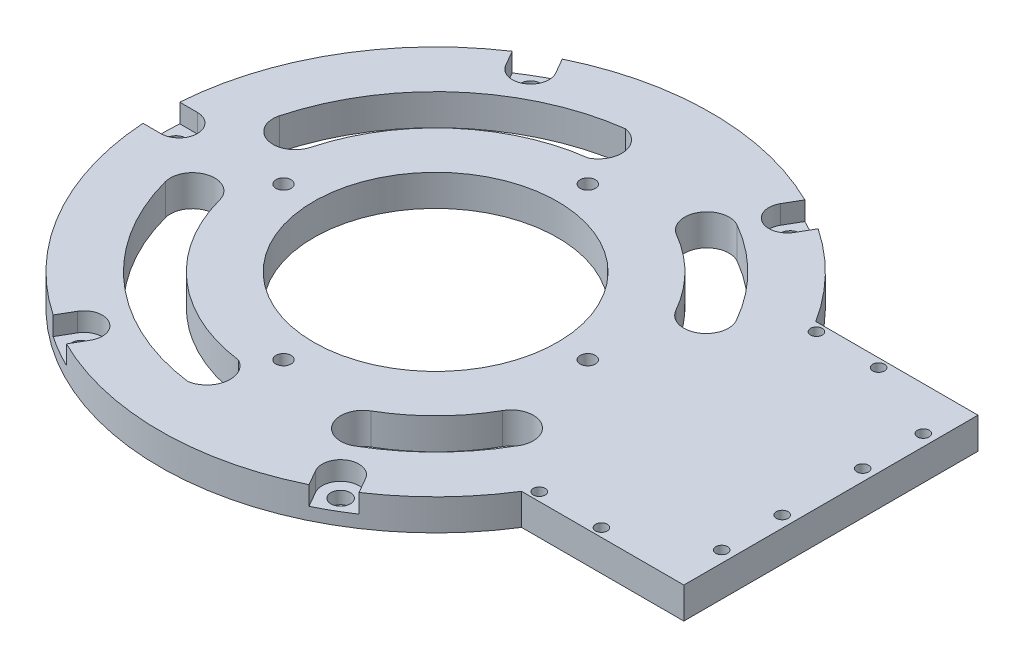
SolidWorks part; units mm, degrees
note: '?' marks a value the reader was unsure of.
material "6061 Alloy"
ref_plane "Front Plane" through (0, 0, 0) normal (0, 0, 1) x (1, 0, 0)
ref_plane "Top Plane" through (0, 0, 0) normal (0, 1, 0) x (1, 0, 0)
ref_plane "Right Plane" through (0, 0, 0) normal (1, 0, 0) x (0, 0, -1)
sketch "Sketch1" plane through (0, 0, 0) normal (0, 1, 0) x (1, 0, 0)
  line L0 (164.381, 61.17) -> (96.9054, 61.17)
  line L1 (96.9054, -61.17) -> (164.381, -61.17)
  line L2 (164.381, -61.17) -> (164.381, 61.17)
  arc A0 (96.9054, 61.17) -> (96.9054, -61.17) centre (0, 0) ccw
extrude "Boss-Extrude1" add sketch "Sketch1" against normal blind 13
sketch "Sketch2" plane through (0, -13, 0) normal (0, -1, 0) x (1, 0, 0)
  arc A0 (36.6644, -63.4908) -> (45.9149, -79.5096) centre (41.2896, -71.5002) ccw
  arc A1 (45.9149, -79.5096) -> (79.9701, -45.108) centre (0, 0) ccw
  arc A2 (79.9701, -45.108) -> (63.8586, -36.0201) centre (71.9144, -40.564) ccw
  arc A3 (63.8586, -36.0201) -> (36.6644, -63.4908) centre (0, 0) cw
extrude "Cut-Extrude1" cut sketch "Sketch2" against normal through all
sketch "Sketch3" plane through (0, -13, 0) normal (0, -1, 0) x (1, 0, 0)
  arc A0 (45.9149, 79.5096) -> (36.6644, 63.4908) centre (41.2896, 71.5002) ccw
  arc A1 (36.6644, 63.4908) -> (63.8586, 36.0201) centre (0, 0) cw
  arc A2 (63.8586, 36.0201) -> (79.9701, 45.108) centre (71.9144, 40.564) ccw
  arc A3 (79.9701, 45.108) -> (45.9149, 79.5096) centre (0, 0) ccw
extrude "Cut-Extrude2" cut sketch "Sketch3" against normal through all
sketch "Sketch4" plane through (0, -13, 0) normal (0, -1, 0) x (1, 0, 0)
  arc A0 (-12.0097, -91.0259) -> (-9.2761, -72.7277) centre (-13.7612, -81.411) ccw
  arc A1 (-9.2761, -72.7277) -> (-70.8237, -18.957) centre (0, 0) cw
  arc A2 (-70.8237, -18.957) -> (-88.6926, -23.7399) centre (-79.7581, -21.3484) ccw
  arc A3 (-88.6926, -23.7399) -> (-12.0097, -91.0259) centre (0, 0) ccw
extrude "Cut-Extrude3" cut sketch "Sketch4" against normal through all
sketch "Sketch5" plane through (0, -13, 0) normal (0, -1, 0) x (1, 0, 0)
  arc A0 (-88.6926, 23.7399) -> (-70.8237, 18.957) centre (-79.7581, 21.3484) ccw
  arc A1 (-70.8237, 18.957) -> (-9.2761, 72.7277) centre (0, 0) cw
  arc A2 (-9.2761, 72.7277) -> (-12.0097, 91.0259) centre (-13.7612, 81.411) ccw
  arc A3 (-12.0097, 91.0259) -> (-88.6926, 23.7399) centre (0, 0) ccw
extrude "Cut-Extrude4" cut sketch "Sketch5" against normal through all
sketch "Sketch6" plane through (0, 0, 0) normal (0, 1, 0) x (-1, 0, 0)
  line L0 (114.3626, 7.3237) -> (106.9962, 7.3428)
  line L1 (106.9567, -7.8972) -> (114.3231, -7.9163)
  arc A0 (106.9962, 7.3428) -> (106.9567, -7.8972) centre (106.9765, -0.2772) ccw
  arc A1 (114.3231, -7.9163) -> (114.3626, 7.3237) centre (0, 0) ccw
extrude "Cut-Extrude5" cut sketch "Sketch6" against normal blind 7.8
hole_wizard "1/4 Clearance Hole1" positions "Sketch10" profile "Sketch9" hole size "1/4" standard "ANSI Inch"
sketch "Sketch10" plane through (0, -7.8, 0) normal (0, 1, 0) x (1, 0, 0)
  circle A0 centre (0, 0) radius 107.95
  point P10 (-107.95, 0)
  point P18 (-53.975, 93.4874)
  point P19 (53.975, 93.4874)
  point P25 (53.975, -93.4874)
  point P26 (-53.975, -93.4874)
  point P28 (107.95, 0) [skipped]
  dimension "D1" = 215.9
  dimension "D2" = 6
sketch "Sketch9" plane through (-53.975, -7.8, 93.4874) normal (1, 0, 0) x (0, 0, 1)
  line L0 (0, 0) -> (0, 5.2)
  line L1 (0, 5.2) -> (4.064, 5.2)
  line L2 (4.064, 5.2) -> (4.064, 0)
  line L5 (4.064, 0) -> (0, 0)
  line L11 (0, -6.35) -> (0, 107.95) construction
  dimension "Thru Hole Dia." = 8.128
  dimension "Thru Hole Depth" = 5.2
hole_wizard "Hole1" positions "Sketch12" profile "Sketch11" legacy
sketch "Sketch12" plane through (0, 0, 0) normal (0, 1, 0) x (1, 0, 0)
  point P0 (63.27, 0)
  point P1 (0, -63.27)
  point P2 (-63.27, 0)
  point P3 (0, 63.27)
sketch "Sketch11" plane through (63.27, 0, 0) normal (1, 0, 0) x (0, 0, 1)
  line L0 (0, 0) -> (0, 13)
  line L1 (0, 13) -> (3.15, 13)
  line L2 (3.15, 13) -> (3.15, 0)
  line L3 (3.15, 0) -> (0, 0)
  line L4 (0, 110) -> (0, -10) construction
  dimension "Diameter" = 6.3
  dimension "Depth" = 13
hole_wizard "Hole2" positions "Sketch14" profile "Sketch13" legacy
sketch "Sketch14" plane through (0, 0, 0) normal (0, 1, 0) x (1, 0, 0)
  point P0 (0, 0)
sketch "Sketch13" plane through (0, 0, 0) normal (1, 0, 0) x (0, 0, 1)
  line L0 (0, 0) -> (0, 13)
  line L1 (0, 13) -> (50.72, 13)
  line L2 (50.72, 13) -> (50.72, 0)
  line L3 (50.72, 0) -> (0, 0)
  line L4 (0, 110) -> (0, -10) construction
  dimension "Diameter" = 101.44
  dimension "Depth" = 13
hole_wizard "#8 Clearance Hole1" positions "Sketch16" profile "Sketch15" hole size "#8" standard "ANSI Inch"
sketch "Sketch16" plane through (0, -13, 0) normal (0, -1, 0) x (-1, 0, 0)
  point P0 (-159.641, -40.6683)
  point P1 (-159.641, 17.9645)
  point P2 (-126.5789, 57.63)
  point P3 (-126.5789, -57.63)
  point P4 (-159.641, 43.1626)
  point P5 (-159.641, -15.5005)
  point P6 (-100.7209, 57.63)
  point P7 (-100.7209, -57.63)
sketch "Sketch15" plane through (159.641, -13, 40.6683) normal (1, 0, 0) x (0, 0, -1)
  line L0 (0, 0) -> (0, 13)
  line L1 (0, 13) -> (2.44, 13)
  line L2 (2.44, 13) -> (2.44, 0)
  line L5 (2.44, 0) -> (0, 0)
  line L11 (0, -6.35) -> (0, 107.95) construction
  dimension "Thru Hole Dia." = 4.88
  dimension "Thru Hole Depth" = 13
ref_axis "Axis1" through (0, -13, 0) along (0, 1, 0)?
pattern_circular "CirPattern2" count 6 over 360 about axis through (0, 0, 0) along (0, 1, 0) skipping 3 of "Cut-Extrude5"
